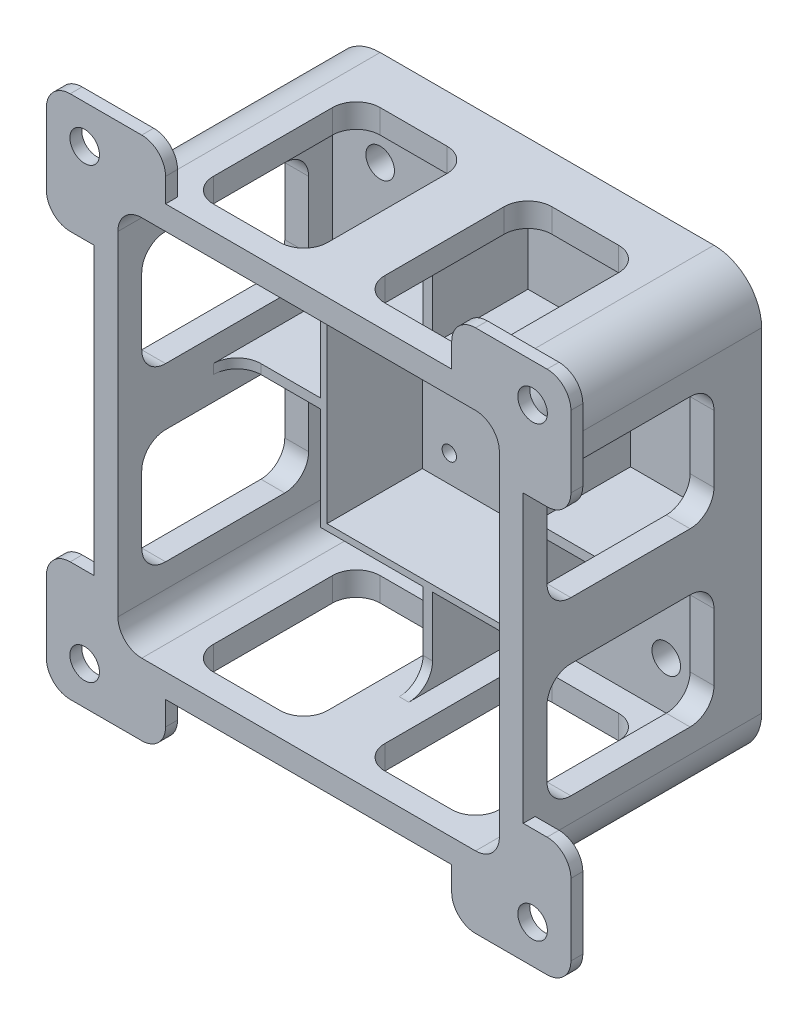
SolidWorks part; units mm, degrees
material "尼龙 101"
ref_plane "前视基准面" through (0, 0, 0) normal (0, 0, 1) x (1, 0, 0)
ref_plane "上视基准面" through (0, 0, 0) normal (0, 1, 0) x (1, 0, 0)
ref_plane "右视基准面" through (0, 0, 0) normal (1, 0, 0) x (0, 0, -1)
sketch "草图1" plane through (0, 0, 0) normal (0, 0, 1) x (1, 0, 0)
  line L1 (-35, 45) -> (35, 45)
  line L2 (-45, 35) -> (-45, -35)
  line L3 (-35, -45) -> (35, -45)
  line L4 (45, 35) -> (45, -35)
  line L5 (-45, 45) -> (45, -45) construction
  line L6 (-45, -45) -> (45, 45) construction
  arc A0 (-45, -35) -> (-35, -45) centre (-35, -35) ccw
  arc A1 (35, -45) -> (45, -35) centre (35, -35) ccw
  arc A2 (35, 45) -> (45, 35) centre (35, 35) cw
  arc A3 (-35, 45) -> (-45, 35) centre (-35, 35) ccw
  point P0 (0, 0)
  dimension "D3" = 10
  dimension "D1" = 90
  dimension "D2" = 90
extrude "凸台-拉伸1" add sketch "草图1" along normal blind 50
shell "抽壳1" thickness 5 removed face at (0, 0, 50)
sketch "草图3" plane through (0, 0, 50) normal (0, 0, 1) x (1, 0, 0)
  line L1 (0, 0) -> (0, 55.6478) construction
  line L2 (0, 0) -> (103.6974, 0) construction
  circle A0 centre (-30, 30) radius 3
  circle A1 centre (30, 30) radius 3
  circle A2 centre (30, -30) radius 3
  circle A3 centre (-30, -30) radius 3
  dimension "D3" = 6
  dimension "D4" = 6
  dimension "D5" = 6
  dimension "D6" = 6
  dimension "D1" = 60
  dimension "D2" = 60
extrude "切除-拉伸1" cut sketch "草图3" against normal up to next
sketch "草图4" plane through (0, 0, 5) normal (0, 0, 1) x (1, 0, 0)
  line L1 (-21.15, -21.15) -> (21.15, -21.15)
  line L2 (-21.15, -21.15) -> (-21.15, 21.15)
  line L3 (-21.15, 21.15) -> (21.15, 21.15)
  line L4 (21.15, -21.15) -> (21.15, 21.15)
  line L5 (-21.15, -21.15) -> (21.15, 21.15) construction
  line L6 (-21.15, 21.15) -> (21.15, -21.15) construction
  line L7 (-22.5, -22.5) -> (22.5, -22.5)
  line L8 (-22.5, -22.5) -> (-22.5, 22.5)
  line L9 (-22.5, 22.5) -> (22.5, 22.5)
  line L10 (22.5, -22.5) -> (22.5, 22.5)
  line L11 (-22.5, -22.5) -> (22.5, 22.5) construction
  line L12 (-22.5, 22.5) -> (22.5, -22.5) construction
  point P0 (0, 0)
  point P6 (0, 0)
  dimension "D1" = 42.3
  dimension "D2" = 42.3
  dimension "D3" = 45
  dimension "D4" = 45
extrude "凸台-拉伸3" add sketch "草图4" along normal blind 20
sketch "草图11" plane through (0, 0, 5) normal (0, 0, 1) x (1, 0, 0)
  line L0 (-15.5, -15.5) -> (-15.5, 15.5) construction
  line L1 (-15.5, 15.5) -> (15.5, 15.5) construction
  line L2 (15.5, 15.5) -> (15.5, -15.5) construction
  line L3 (15.5, -15.5) -> (-15.5, -15.5) construction
  line L4 (0, 0) -> (34.4126, 0) construction
  line L5 (0, 0) -> (0, 49.7231) construction
  circle A0 centre (-15.5, -15.5) radius 1.5
  circle A1 centre (15.5, -15.5) radius 1.5
  circle A2 centre (15.5, 15.5) radius 1.5
  circle A3 centre (-15.5, 15.5) radius 1.5
  dimension "D3" = 3
  dimension "D4" = 3
  dimension "D5" = 3
  dimension "D6" = 3
  dimension "D1" = 31
  dimension "D2" = 31
extrude "切除-拉伸4" cut sketch "草图11" against normal through all
sketch "草图7" plane through (0, 0, 5) normal (0, 0, 1) x (1, 0, 0)
  line L0 (22.5, 22.5) -> (-22.5, 22.5) construction
  line L1 (-1, 40) -> (1, 40)
  line L2 (-1, 40) -> (-1, 22.5)
  line L3 (-1, 22.5) -> (1, 22.5)
  line L4 (1, 40) -> (1, 22.5)
  line L5 (-1, 40) -> (1, 22.5) construction
  line L6 (-1, 22.5) -> (1, 40) construction
  line L7 (-35, -40) -> (35, -40) construction
  line L8 (-1, -22.5) -> (1, -22.5)
  line L9 (-1, -22.5) -> (-1, -40)
  line L10 (-1, -40) -> (1, -40)
  line L11 (1, -22.5) -> (1, -40)
  line L12 (-1, -22.5) -> (1, -40) construction
  line L13 (-1, -40) -> (1, -22.5) construction
  line L14 (0, 31.25) -> (0, 0) construction
  line L15 (0, 0) -> (0, -31.25) construction
  line L16 (35, 40) -> (-35, 40) construction
  line L17 (-22.5, -22.5) -> (22.5, -22.5) construction
  point P0 (0, 31.25)
  point P7 (0, -31.25)
  dimension "D1" = 2
  dimension "D2" = 2
extrude "凸台-拉伸5" add sketch "草图7" along normal up to surface (20 mm away) up to face at (0, 0, 25)
ref_axis "基准轴1" through (0, 0, -2) along (0, 0, 1)
pattern_circular "阵列(圆周)1" count 2 over 90 about axis through (0, 0, -2) along (0, 0, 1) of "凸台-拉伸5"
sketch "草图10" plane through (0, 0, 0) normal (0, 0, -1) x (-1, 0, 0)
  circle A0 centre (0, 0) radius 5
  dimension "D1" = 10
extrude "切除-拉伸3" cut sketch "草图10" against normal through all
fillet "圆角1" radius 5 4 edges at (-40, 0, 25) (40, 0, 25) (0, -40, 25) (0, 40, 25)
sketch "草图12" plane through (0, 0, 50) normal (0, 0, 1) x (1, 0, 0)
  line L5 (40, -30) -> (50, -30)
  line L6 (30, -40) -> (30, -50)
  line L7 (35, -55) -> (50, -55)
  line L8 (55, -35) -> (55, -50)
  line L19 (40, -35) -> (40, 35) construction
  line L20 (35, -40) -> (30, -40)
  line L21 (-35, -40) -> (35, -40) construction
  line L22 (40, -35) -> (40, -30)
  line L23 (0, 0) -> (0, -109.4281) construction
  line L24 (-40, -35) -> (-40, -30)
  line L25 (-35, -40) -> (-30, -40)
  line L27 (-55, -35) -> (-55, -50)
  line L28 (-35, -55) -> (-50, -55)
  line L29 (-30, -40) -> (-30, -50)
  line L30 (-40, -30) -> (-50, -30)
  line L36 (45, -35) -> (45, 35) construction
  line L37 (-35, -45) -> (35, -45) construction
  line L38 (0, 0) -> (81.8006, 0) construction
  line L39 (-40, 30) -> (-50, 30)
  line L40 (-30, 40) -> (-30, 50)
  line L41 (-35, 55) -> (-50, 55)
  line L42 (-55, 35) -> (-55, 50)
  line L43 (-35, 40) -> (-30, 40)
  line L44 (-40, 35) -> (-40, 30)
  line L45 (40, 35) -> (40, 30)
  line L46 (35, 40) -> (30, 40)
  line L47 (55, 35) -> (55, 50)
  line L48 (35, 55) -> (50, 55)
  line L49 (30, 40) -> (30, 50)
  line L50 (40, 30) -> (50, 30)
  arc A1 (-40, 35) -> (-35, 40) centre (-35, 35) cw
  arc A2 (-30, 50) -> (-35, 55) centre (-35, 50) ccw
  arc A3 (-50, 55) -> (-55, 50) centre (-50, 50) ccw
  arc A4 (40, -35) -> (35, -40) centre (35, -35) cw
  arc A5 (30, -50) -> (35, -55) centre (35, -50) ccw
  arc A6 (50, -55) -> (55, -50) centre (50, -50) ccw
  arc A7 (50, -30) -> (55, -35) centre (50, -35) cw
  arc A22 (-50, -30) -> (-55, -35) centre (-50, -35) ccw
  arc A23 (-50, -55) -> (-55, -50) centre (-50, -50) cw
  arc A24 (-30, -50) -> (-35, -55) centre (-35, -50) cw
  arc A25 (-40, -35) -> (-35, -40) centre (-35, -35) ccw
  arc A27 (-50, 30) -> (-55, 35) centre (-50, 35) cw
  arc A28 (50, 30) -> (55, 35) centre (50, 35) ccw
  arc A29 (50, 55) -> (55, 50) centre (50, 50) cw
  arc A30 (30, 50) -> (35, 55) centre (35, 50) cw
  arc A31 (40, 35) -> (35, 40) centre (35, 35) ccw
  dimension "D5" = 5
  dimension "D6" = 10
  dimension "D3" = 25
  dimension "D4" = 25
  dimension "D7" = 10
extrude "凸台-拉伸6" add sketch "草图12" against normal blind 2.5
sketch "草图13" plane through (0, 0, 47.5) normal (0, 0, -1) x (-1, 0, 0)
  line L0 (-55, -50) -> (-55, -35) construction
  line L1 (-35, -55) -> (-50, -55) construction
  line L2 (-55, 35) -> (-55, 50) construction
  line L3 (-50, 55) -> (-35, 55) construction
  line L4 (55, 50) -> (55, 35) construction
  line L5 (35, 55) -> (50, 55) construction
  line L6 (50, -55) -> (35, -55) construction
  line L7 (55, -35) -> (55, -50) construction
  circle A0 centre (-46.97, -46.97) radius 3.1
  circle A1 centre (-46.97, 46.97) radius 3.1
  circle A2 centre (46.97, 46.97) radius 3.1
  circle A3 centre (46.97, -46.97) radius 3.1
  dimension "D9" = 6.2
  dimension "D10" = 6.2
  dimension "D11" = 6.2
  dimension "D12" = 6.2
  dimension "D1" = 8.03
  dimension "D2" = 8.03
  dimension "D3" = 8.03
  dimension "D4" = 8.03
  dimension "D5" = 8.03
  dimension "D6" = 8.03
  dimension "D7" = 8.03
  dimension "D8" = 8.03
extrude "切除-拉伸5" cut sketch "草图13" against normal through all
sketch "草图14" plane through (0, 40, 0) normal (0, -1, 0) x (1, 0, 0)
  line L0 (35, 50) -> (35, 5) construction
  line L1 (25, 45) -> (11, 45)
  line L2 (30, 40) -> (30, 15)
  line L3 (25, 10) -> (11, 10)
  line L4 (6, 40) -> (6, 15)
  line L5 (35, 5) -> (1, 5) construction
  line L6 (1, 30) -> (1, 5) construction
  line L7 (35, 50) -> (-35, 50) construction
  line L8 (0, 0) -> (0, 105.1469) construction
  line L9 (-6, 40) -> (-6, 15)
  line L10 (-25, 10) -> (-11, 10)
  line L11 (-30, 40) -> (-30, 15)
  line L12 (-25, 45) -> (-11, 45)
  arc A0 (11, 45) -> (6, 40) centre (11, 40) ccw
  arc A1 (11, 10) -> (6, 15) centre (11, 15) cw
  arc A2 (30, 15) -> (25, 10) centre (25, 15) cw
  arc A3 (25, 45) -> (30, 40) centre (25, 40) cw
  arc A4 (-25, 45) -> (-30, 40) centre (-25, 40) ccw
  arc A5 (-30, 15) -> (-25, 10) centre (-25, 15) ccw
  arc A6 (-11, 10) -> (-6, 15) centre (-11, 15) ccw
  arc A7 (-11, 45) -> (-6, 40) centre (-11, 40) cw
  dimension "D5" = 5
  dimension "D1" = 5
  dimension "D2" = 5
  dimension "D3" = 5
  dimension "D4" = 5
extrude "切除-拉伸6" cut sketch "草图14" against normal through all
sketch "草图15" plane through (0, -40, 0) normal (0, 1, 0) x (1, 0, 0)
  line L0 (30, -15) -> (30, -40) construction
  line L1 (25, -45) -> (11, -45) construction
  line L2 (6, -40) -> (6, -15) construction
  line L3 (11, -10) -> (25, -10) construction
  line L4 (30, -15) -> (30, -40)
  line L5 (25, -45) -> (11, -45)
  line L6 (6, -40) -> (6, -15)
  line L7 (11, -10) -> (25, -10)
  line L8 (-6, -15) -> (-6, -40) construction
  line L9 (-11, -45) -> (-25, -45) construction
  line L10 (-30, -40) -> (-30, -15) construction
  line L11 (-25, -10) -> (-11, -10) construction
  line L12 (-25, -10) -> (-11, -10)
  line L13 (-30, -40) -> (-30, -15)
  line L14 (-6, -15) -> (-6, -40)
  line L15 (-11, -45) -> (-25, -45)
  arc A0 (25, -45) -> (30, -40) centre (25, -40) ccw construction
  arc A1 (6, -40) -> (11, -45) centre (11, -40) ccw construction
  arc A2 (11, -10) -> (6, -15) centre (11, -15) ccw construction
  arc A3 (30, -15) -> (25, -10) centre (25, -15) ccw construction
  arc A4 (25, -45) -> (30, -40) centre (25, -40) ccw
  arc A5 (6, -40) -> (11, -45) centre (11, -40) ccw
  arc A6 (11, -10) -> (6, -15) centre (11, -15) ccw
  arc A7 (30, -15) -> (25, -10) centre (25, -15) ccw
  arc A8 (-11, -45) -> (-6, -40) centre (-11, -40) ccw construction
  arc A9 (-30, -40) -> (-25, -45) centre (-25, -40) ccw construction
  arc A10 (-25, -10) -> (-30, -15) centre (-25, -15) ccw construction
  arc A11 (-6, -15) -> (-11, -10) centre (-11, -15) ccw construction
  arc A12 (-6, -15) -> (-11, -10) centre (-11, -15) ccw
  arc A13 (-25, -10) -> (-30, -15) centre (-25, -15) ccw
  arc A14 (-30, -40) -> (-25, -45) centre (-25, -40) ccw
  arc A15 (-11, -45) -> (-6, -40) centre (-11, -40) ccw
extrude "切除-拉伸7" cut sketch "草图15" against normal through all
pattern_circular "阵列(圆周)2" count 4 over 360 about axis through (0, 0, -2) along (0, 0, 1) of "切除-拉伸6"
